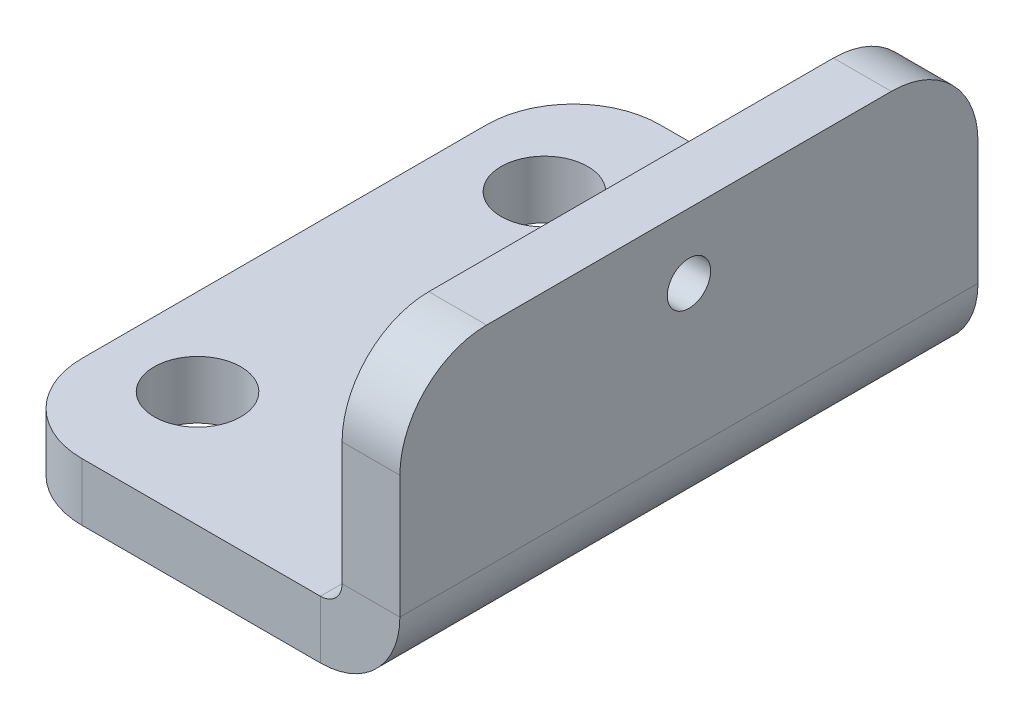
SolidWorks part; units mm, degrees
note: The reader was unsure of these and kept them because the rebuilt part matched: bend radius of "BaseBend1".
ref_plane "Front Plane" through (0, 0, 0) normal (0, 0, 1) x (1, 0, 0)
ref_plane "Top Plane" through (0, 0, 0) normal (0, 1, 0) x (1, 0, 0)
ref_plane "Right Plane" through (0, 0, 0) normal (1, 0, 0) x (0, 0, -1)
sketch "Sketch1" plane through (0, 0, 0) normal (0, 0, 1) x (1, 0, 0)
  line L0 (-12, 0) -> (0, 0)
  line L1 (0, 0) -> (0, 8)
  dimension "D1" = 8
  dimension "D2" = 12
base flange "Base-Flange1" sketch "Sketch1" end condition mid plane depth 20 reverse direction no thickness 2 reverse thickness direction no bend radius 0.75
bend "BaseBend1" bend radius 0.75 bend angle 90 parameters "D5"=1
fillet "Fillet1" radius 3 4 edges at (-12, -1, 10) (-12, -1, -10) (1, 8, -10) (1, 8, 10)
sketch "Sketch6" plane through (0, 0, 0) normal (0, 1, 0) x (1, 0, 0)
  line L0 (-12, -7) -> (-12, 7) construction
  line L1 (0, 0) -> (-12, 0) construction
  circle A0 centre (-9, 6) radius 1.5
  circle A1 centre (-9, -6) radius 1.5
  dimension "D2" = 3
  dimension "D1" = 3
  dimension "D3" = 6
extrude "Cut-Extrude1" cut sketch "Sketch6" against normal through all normal cut yes
sketch "Sketch7" plane through (0, 0, 0) normal (-1, 0, 0) x (0, 0, 1)
  line L0 (0, 0) -> (0, 8) construction
  circle A0 centre (0, 5.75) radius 0.75
  circle A1 centre (0, 5.75) radius 0.75 construction
  dimension "D1" = 1.5
extrude "Cut-Extrude2" cut sketch "Sketch7" against normal through all normal cut yes
sketch "Bend-Lines1" [suppressed] plane through (0, 0, 0) normal (0, 1, 0) x (1, 0, 0)
sketch "Bounding-Box1" [suppressed] plane through (0, 0, 0) normal (0, 1, 0) x (1, 0, 0)
sheet metal parameters "Sheet-Metal1" thickness 2 parameters "D1"=0.75
flat pattern "Flat-Pattern1" [suppressed]
sketch "Bend-Lines2" plane through (0, 0, 0) normal (0, 1, 0) x (1, 0, 0)
  line L0 (0.436, 10) -> (0.436, -10) construction
  line L1 (0.436, 10) -> (0.436, -10) construction
sketch3d "Bounding-Box2" [suppressed]
  line L0 (0, 0, 0) -> (20.8719, 0, 0) construction
  line L1 (0, 20, 0) -> (20.8719, 20, 0) construction
  line L2 (0, 0, 0) -> (0, 20, 0) construction
  line L3 (20.8719, 0, 0) -> (20.8719, 20, 0) construction
bend of the flat pattern "Flatten-<BaseBend1>1"
sheet metal parameters "Sheet-Metal2" thickness 2 parameters "D1"=0.75
flat pattern "Flat-Pattern1"
sketch "Bend-Lines2" plane through (0, 0, 0) normal (0, 1, 0) x (1, 0, 0)
  line L0 (0.436, 10) -> (0.436, -10) construction
  line L1 (0.436, 10) -> (0.436, -10) construction
sketch3d "Bounding-Box2" [suppressed]
  line L0 (0, 0, 0) -> (20.8719, 0, 0) construction
  line L1 (0, 20, 0) -> (20.8719, 20, 0) construction
  line L2 (0, 0, 0) -> (0, 20, 0) construction
  line L3 (20.8719, 0, 0) -> (20.8719, 20, 0) construction
bend of the flat pattern "Flatten-<BaseBend1>1"
sheet metal parameters "Sheet-Metal3" thickness 2 parameters "D1"=0.75
flat pattern "Flat-Pattern1"
sketch "Bend-Lines2" plane through (0, 0, 0) normal (0, 1, 0) x (1, 0, 0)
  line L0 (0.436, 10) -> (0.436, -10) construction
  line L1 (0.436, 10) -> (0.436, -10) construction
sketch3d "Bounding-Box2" [suppressed]
  line L0 (0, 0, 0) -> (20.8719, 0, 0) construction
  line L1 (0, 20, 0) -> (20.8719, 20, 0) construction
  line L2 (0, 0, 0) -> (0, 20, 0) construction
  line L3 (20.8719, 0, 0) -> (20.8719, 20, 0) construction
bend of the flat pattern "Flatten-<BaseBend1>1"
